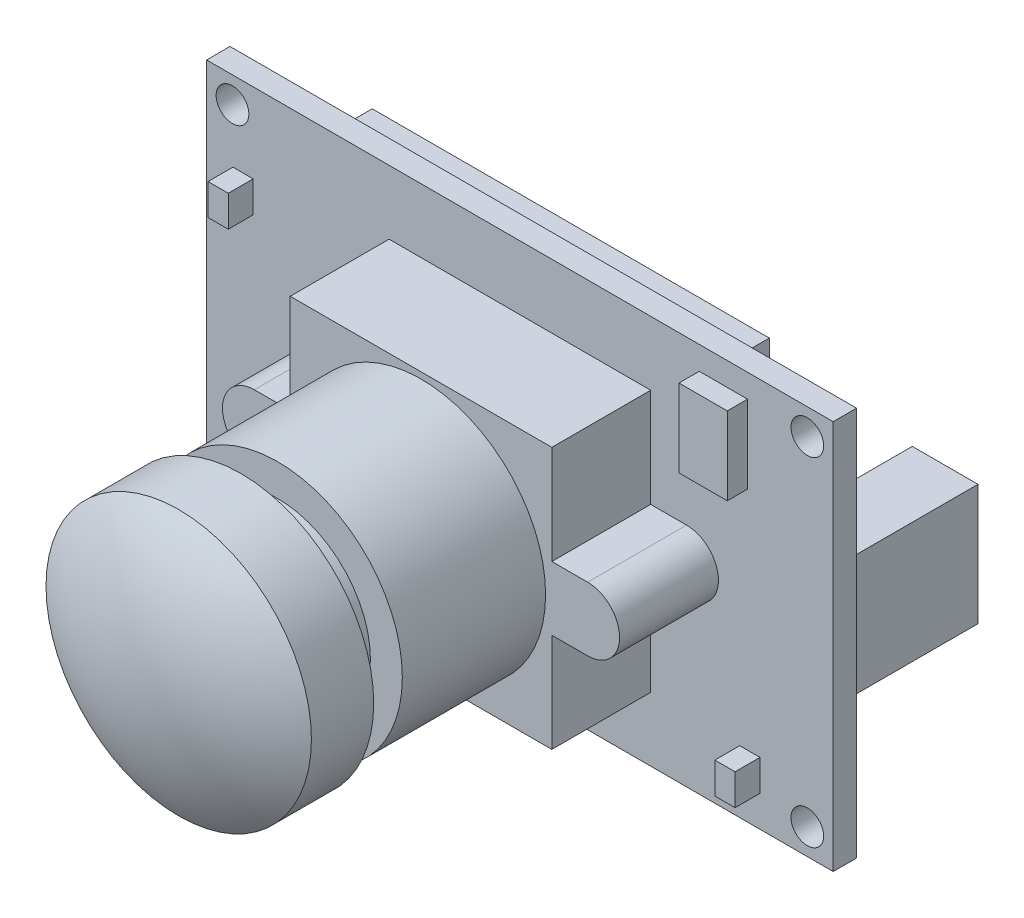
SolidWorks part; units mm, degrees
material "Camera"
ref_plane "Front Plane" through (0, 0, 0) normal (0, 0, 1) x (1, 0, 0)
ref_plane "Top Plane" through (0, 0, 0) normal (0, 1, 0) x (1, 0, 0)
ref_plane "Right Plane" through (0, 0, 0) normal (1, 0, 0) x (0, 0, -1)
sketch "Sketch2" plane through (0, 0, 0) normal (0, 0, 1) x (1, 0, 0)
  line L0 (0, 0) -> (0, 6.003) construction
  line L1 (20.1168, 12.5095) -> (-20.1168, 12.5095)
  line L2 (20.1168, 12.5095) -> (20.1168, -12.5095)
  line L3 (20.1168, -12.5095) -> (-20.1168, -12.5095)
  line L4 (-20.1168, 12.5095) -> (-20.1168, -12.5095)
  line L5 (20.1168, 12.5095) -> (-20.1168, -12.5095) construction
  line L6 (20.1168, -12.5095) -> (-20.1168, 12.5095) construction
  line L7 (-1000, 0) -> (49000, 0) construction
  circle A0 centre (-18.4568, 10.8495) radius 1.05
  circle A1 centre (-18.4568, -10.8495) radius 1.05
  circle A2 centre (18.4568, -10.8495) radius 1.05
  circle A3 centre (18.4568, 10.8495) radius 1.05
  point P0 (0, 0)
  dimension "D5" = 2.1
  dimension "D1" = 40.2336
  dimension "D2" = 25.019
  dimension "D3" = 1.66
  dimension "D4" = 1.66
extrude "Boss-Extrude1" add sketch "Sketch2" along normal blind 1.5
sketch "Sketch3" plane through (0, 0, 1.5) normal (0, 0, 1) x (1, 0, 0)
  line L0 (-8.4, -2.05) -> (-8.4, -8.4)
  line L1 (8.4, 8.4) -> (-8.4, 8.4)
  line L2 (8.4, 8.4) -> (8.4, 2.05)
  line L3 (8.4, -8.4) -> (-8.4, -8.4)
  line L4 (-8.4, 8.4) -> (-8.4, 2.05)
  line L5 (8.4, 8.4) -> (-8.4, -8.4) construction
  line L6 (8.4, -8.4) -> (-8.4, 8.4) construction
  line L7 (-10.7, 2.05) -> (-8.4, 2.05)
  line L8 (0, -1000) -> (0, 49000) construction
  line L9 (-10.7, -2.05) -> (-8.4, -2.05)
  line L10 (10.7, 2.05) -> (8.4, 2.05)
  line L11 (10.7, -2.05) -> (8.4, -2.05)
  line L12 (8.4, -2.05) -> (8.4, -8.4)
  line L13 (-1000, 0) -> (49000, 0) construction
  arc A0 (-10.7, 2.05) -> (-10.7, -2.05) centre (-10.7, 0) ccw
  arc A1 (10.7, 2.05) -> (10.7, -2.05) centre (10.7, 0) cw
  point P0 (0, 0)
  dimension "D1" = 16.8
  dimension "D2" = 16.8
  dimension "D3" = 4.1
  dimension "D4" = 2.3
extrude "Boss-Extrude2" add sketch "Sketch3" along normal blind 6.35
sketch "Sketch4" plane through (0, 0, 7.85) normal (0, 0, 1) x (1, 0, 0)
  circle A0 centre (0, 0) radius 8
  dimension "D1" = 16
extrude "Boss-Extrude3" add sketch "Sketch4" along normal blind 9.2
sketch "Sketch5" plane through (0, 0, 17.05) normal (0, 0, 1) x (1, 0, 0)
  circle A0 centre (0, 0) radius 5.95
  dimension "D1" = 11.9
extrude "Boss-Extrude4" add sketch "Sketch5" along normal blind 2.36
sketch "Sketch6" plane through (0, 0, 19.41) normal (0, 0, 1) x (1, 0, 0)
  circle A0 centre (0, 0) radius 8.5217
  dimension "D1" = 17.0434
extrude "Lens" add sketch "Sketch6" along normal blind 4
sketch "Sketch7" plane through (0, 0, 0) normal (0, 0, -1) x (-1, 0, 0)
  line L0 (0, 0) -> (-20.1168, 0) construction
  line L1 (-15.3968, -3.875) -> (-19.6168, -3.875)
  line L2 (-15.3968, -3.875) -> (-15.3968, 3.875)
  line L3 (-15.3968, 3.875) -> (-19.6168, 3.875)
  line L4 (-19.6168, -3.875) -> (-19.6168, 3.875)
  line L5 (-20.1168, -12.5095) -> (-20.1168, 12.5095) construction
  point P9 (-19.6168, 0)
  dimension "D1" = 7.75
  dimension "D2" = 4.22
  dimension "D3" = 0.5
extrude "Boss-Extrude6" add sketch "Sketch7" along normal blind 8.3
sketch "Sketch8" plane through (0, 0, 0) normal (0, 0, -1) x (-1, 0, 0)
  line L0 (20.1168, 12.5095) -> (20.1168, -12.5095) construction
  line L1 (15.6768, -10.8695) -> (6.6768, -10.8695)
  line L2 (15.6768, -10.8695) -> (15.6768, -7.9395)
  line L3 (15.6768, -7.9395) -> (6.6768, -7.9395)
  line L4 (6.6768, -10.8695) -> (6.6768, -7.9395)
  line L5 (20.1168, -12.5095) -> (-20.1168, -12.5095) construction
  dimension "D1" = 4.44
  dimension "D2" = 1.64
  dimension "D3" = 9
  dimension "D4" = 2.93
extrude "Boss-Extrude7" add sketch "Sketch8" along normal blind 4.35
sketch "Sketch9" plane through (0, 0, 1.5) normal (0, 0, 1) x (1, 0, 0)
  line L0 (20.1168, -12.5095) -> (20.1168, 12.5095) construction
  line L1 (11.5168, 11.0095) -> (14.6168, 11.0095)
  line L2 (11.5168, 11.0095) -> (11.5168, 6.0095)
  line L3 (11.5168, 6.0095) -> (14.6168, 6.0095)
  line L4 (14.6168, 11.0095) -> (14.6168, 6.0095)
  line L5 (20.1168, 12.5095) -> (-20.1168, 12.5095) construction
  dimension "D1" = 3.1
  dimension "D2" = 5
  dimension "D3" = 5.5
  dimension "D4" = 1.5
extrude "Boss-Extrude8" add sketch "Sketch9" along normal blind 1.3
sketch "Sketch10" plane through (0, 0, 0) normal (0, 0, -1) x (-1, 0, 0)
  line L0 (-20.1168, -12.5095) -> (-20.1168, 12.5095) construction
  line L1 (-13.1168, 12.2095) -> (12.3832, 12.2095)
  line L2 (-13.1168, 12.2095) -> (-13.1168, 4.2095)
  line L3 (-13.1168, 4.2095) -> (12.3832, 4.2095)
  line L4 (12.3832, 12.2095) -> (12.3832, 4.2095)
  line L5 (-13.1168, 12.2095) -> (12.3832, 4.2095) construction
  line L6 (-13.1168, 4.2095) -> (12.3832, 12.2095) construction
  line L7 (-20.1168, 12.5095) -> (20.1168, 12.5095) construction
  point P0 (-0.3668, 8.2095)
  dimension "D1" = 25.5
  dimension "D2" = 8
  dimension "D3" = 7
  dimension "D4" = 0.3
extrude "Boss-Extrude9" add sketch "Sketch10" along normal blind 1.4
sketch "Sketch11" plane through (0, 0, 1.5) normal (0, 0, 1) x (1, 0, 0)
  line L0 (20.1168, -12.5095) -> (20.1168, 12.5095) construction
  line L1 (15.4168, -10.5095) -> (14.1168, -10.5095)
  line L2 (15.4168, -10.5095) -> (15.4168, -8.5095)
  line L3 (15.4168, -8.5095) -> (14.1168, -8.5095)
  line L4 (14.1168, -10.5095) -> (14.1168, -8.5095)
  line L5 (-20.1168, -12.5095) -> (20.1168, -12.5095) construction
  line L6 (-17.1271, 5.3916) -> (-18.4271, 5.3916)
  line L7 (-17.1271, 5.3916) -> (-17.1271, 7.3916)
  line L8 (-17.1271, 7.3916) -> (-18.4271, 7.3916)
  line L9 (-18.4271, 5.3916) -> (-18.4271, 7.3916)
  dimension "D1" = 1.3
  dimension "D2" = 2
  dimension "D3" = 6
  dimension "D4" = 2
extrude "Boss-Extrude10" add sketch "Sketch11" along normal blind 1.6
sketch "Sketch12" plane through (0, 0, 0) normal (0, 0, -1) x (-1, 0, 0)
  line L0 (-20.1168, 12.5095) -> (20.1168, 12.5095) construction
  line L1 (19.1168, 5.1095) -> (16.1168, 5.1095)
  line L2 (19.1168, 5.1095) -> (19.1168, 8.1095)
  line L3 (19.1168, 8.1095) -> (16.1168, 8.1095)
  line L4 (16.1168, 5.1095) -> (16.1168, 8.1095)
  line L5 (20.1168, 12.5095) -> (20.1168, -12.5095) construction
  dimension "D1" = 3
  dimension "D2" = 3
  dimension "D3" = 7.4
  dimension "D4" = 1
extrude "Boss-Extrude11" add sketch "Sketch12" along normal blind 1.4
sketch "Sketch13" plane through (0, 0, 0) normal (0, 0, -1) x (-1, 0, 0)
  line L0 (-20.1168, -12.5095) -> (-20.1168, 12.5095) construction
  line L1 (-14.1478, -9.3853) -> (-10.9728, -9.3853)
  line L2 (-14.1478, -9.3853) -> (-14.1478, -12.0015)
  line L3 (-14.1478, -12.0015) -> (-10.9728, -12.0015)
  line L4 (-10.9728, -9.3853) -> (-10.9728, -12.0015)
  line L5 (20.1168, -12.5095) -> (-20.1168, -12.5095) construction
  line L7 (-7.1628, -7.1755) -> (1.3462, -7.1755)
  line L8 (-7.1628, -7.1755) -> (-7.1628, -12.0015)
  line L9 (-7.1628, -12.0015) -> (1.3462, -12.0015)
  line L10 (1.3462, -7.1755) -> (1.3462, -12.0015)
  dimension "D1" = 3.175
  dimension "D2" = 2.6162
  dimension "D3" = 5.969
  dimension "D4" = 0.508
  dimension "D5" = 8.509
  dimension "D6" = 4.826
  dimension "D7" = 12.954
  dimension "D8" = 0.508
extrude "Boss-Extrude12" add sketch "Sketch13" along normal blind 2.7432
dome "Dome1" faces to dome 1 distance 2.54 reverse direction no elliptical dome no face at (8.5217, 0, 23.41) parameters "D1"=2.54
move or copy body "Body-Move/Copy1" [suppressed] bodies to move or copy 112
